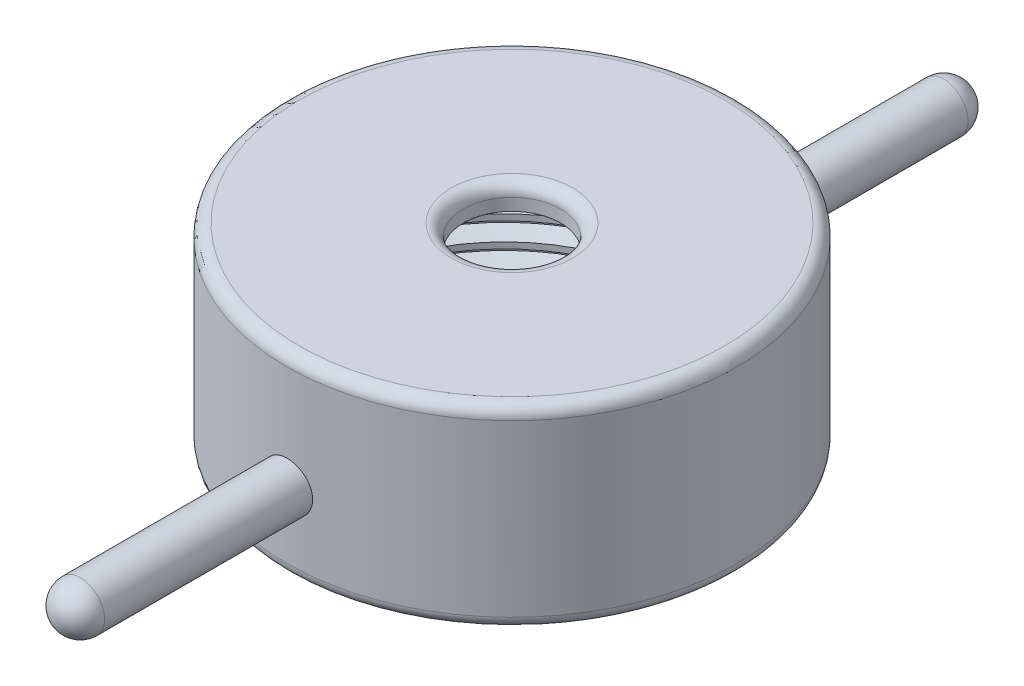
SolidWorks part; units mm, degrees
material "6061-T6 (SS)"
ref_plane "Front Plane" through (0, 0, 0) normal (0, 0, 1) x (1, 0, 0)
ref_plane "Top Plane" through (0, 0, 0) normal (0, 1, 0) x (1, 0, 0)
ref_plane "Right Plane" through (0, 0, 0) normal (1, 0, 0) x (0, 0, -1)
sketch "Sketch1" plane through (0, 0, 0) normal (0, 0, 1) x (1, 0, 0)
  line L0 (28, 0) -> (28, 30)
  line L1 (28, 30) -> (18, 30)
  line L2 (18, 30) -> (18, 28)
  line L3 (18, 28) -> (8, 28)
  line L4 (8, 28) -> (8, 32)
  line L5 (8, 32) -> (37, 32)
  line L6 (37, 32) -> (37, 0)
  line L7 (37, 0) -> (28, 0)
  line L8 (0, 45.0485) -> (0, -12.0889) construction
  dimension "D1" = 32
  dimension "D2" = 4
  dimension "D3" = 9
  dimension "D4" = 2
  dimension "D5" = 28
  dimension "D6" = 18
  dimension "D7" = 8
revolve "Revolve1" add sketch "Sketch1" angle 360 about L8
fillet "Fillet1" radius 2 3 edges at (0, 0, 37) (0, 32, 37) (0, 32, 8)
ref_plane "Plane1" through (0, 0, 75) normal (0, 0, 1) x (1, 0, 0)
sketch "Sketch2" plane through (0, 0, 75) normal (0, 0, 1) x (1, 0, 0)
  circle A0 centre (0, 13) radius 4
  dimension "D1" = 8
  dimension "D2" = 13
extrude "Boss-Extrude1" add sketch "Sketch2" against normal up to surface (38.2168 mm away) up to face at (0, 2, 37)
mirror "Mirror1" about plane through (0, 0, 0) normal (0, 0, 1) of "Boss-Extrude1"
thread "Thread1" pitch 4 method cut profile "Thread Profile1" start angle 0, offset 0, length 28, pitch 4, diameter 56
ref_plane "Plane2" through (28, 0, 0) normal (0, 0, 1) x (1, 0, 0)
sketch "Thread Profile1" plane through (28, 0, 0) normal (0, 0, 1) x (1, 0, 0)
  line L0 (0, 0) -> (0, 4) construction
  line L1 (0, 0) -> (2.1651, 1.25)
  line L2 (2.1651, 1.25) -> (2.1651, 1.75)
  line L3 (2.1651, 1.75) -> (0, 3)
  line L4 (2.1651, 1.5) -> (0, 1.5) construction
  line L11 (0, 0) -> (0, 3)
  point P2 (0, 0)
  dimension "Pitch" = 4
  dimension "Profile_Angle" = 60
  dimension "Profile_Land" = 0.5
  dimension "Profile_Height" = 2.1651
fillet "Fillet2" radius 4 2 edges at (4, 13, -75) (4, 13, 75)
